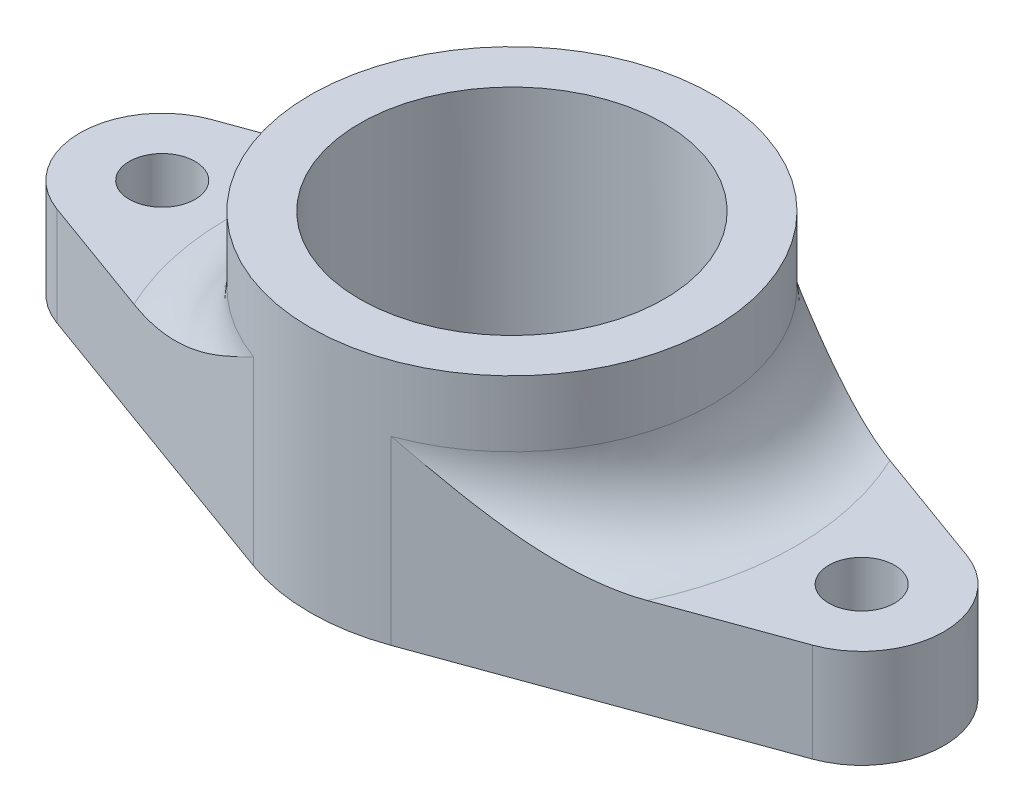
SolidWorks part; units mm, degrees
ref_plane "Front Plane" through (0, 0, 0) normal (0, 0, 1) x (1, 0, 0)
ref_plane "Top Plane" through (0, 0, 0) normal (0, 1, 0) x (1, 0, 0)
ref_plane "Right Plane" through (0, 0, 0) normal (1, 0, 0) x (0, 0, -1)
sketch "Sketch1" plane through (0, 0, 0) normal (0, 1, 0) x (1, 0, 0)
  line L0 (-42.5, 0) -> (42.5, 0) construction
  line L1 (-45.9118, 9.4) -> (-8.3588, 23.03)
  line L2 (45.9118, 9.4) -> (8.3588, 23.03)
  line L3 (0, 0) -> (0, 24.5) construction
  line L4 (45.9118, -9.4) -> (8.3588, -23.03)
  line L5 (-45.9118, -9.4) -> (-8.3588, -23.03)
  line L6 (-43.8647, 3.76) -> (-45.9118, 9.4) construction
  line L7 (0, 18.5) -> (0, 24.5) construction
  line L8 (0, -24.5) -> (0, -18.5) construction
  circle A0 centre (0, 0) radius 18.5
  circle A1 centre (-42.5, 0) radius 4
  circle A2 centre (42.5, 0) radius 4
  arc A3 (-45.9118, 9.4) -> (-45.9118, -9.4) centre (-42.5, 0) ccw
  arc A4 (45.9118, -9.4) -> (45.9118, 9.4) centre (42.5, 0) ccw
  arc A5 (-8.3588, -23.03) -> (8.3588, -23.03) centre (0, 0) ccw
  arc A6 (8.3588, 23.03) -> (-8.3588, 23.03) centre (0, 0) ccw
  dimension "D1" = 37
  dimension "D2" = 8
  dimension "D3" = 85
  dimension "D4" = 6
extrude "Boss-Extrude1" add sketch "Sketch1" along normal blind 30
sketch "Sketch2" plane through (0, 30, 0) normal (0, 1, 0) x (1, 0, 0)
  circle A0 centre (0, 0) radius 24.5
  arc A1 (-8.3588, -23.03) -> (8.3588, -23.03) centre (0, 0) ccw construction
extrude "Cut-Extrude1" cut sketch "Sketch2" against normal offset from surface (18 mm away) 12 flip side to cut up to face at (0, 0, 0)
sketch "Sketch3" plane through (0, 0, 0) normal (1, 0, 0) x (0, 0, -1)
  line L0 (32.7798, 18.6737) -> (24.1434, -14.4349)
  line L1 (24.1434, -14.4349) -> (5, 0)
  line L2 (-9.4, 0) -> (9.4, 0) construction
  arc A0 (5, 0) -> (32.7798, 18.6737) centre (5, 30) ccw
  dimension "D1" = 30
  dimension "D2" = 5
extrude "Cut-Extrude2" cut sketch "Sketch3" against normal through all and the other way through all
fillet "Fillet1" radius 10 2 edges at (24.5, 12, 0) (-24.5, 12, 0)
